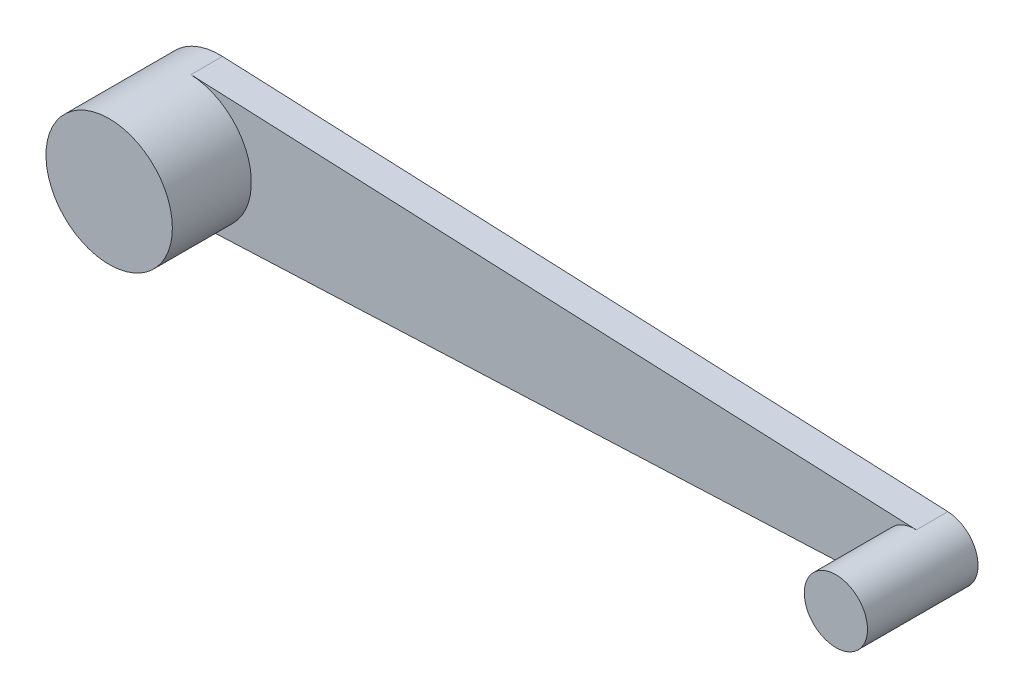
SolidWorks part; units mm, degrees
ref_plane "Front Plane" through (0, 0, 0) normal (0, 0, 1) x (1, 0, 0)
ref_plane "Top Plane" through (0, 0, 0) normal (0, 1, 0) x (1, 0, 0)
ref_plane "Right Plane" through (0, 0, 0) normal (1, 0, 0) x (0, 0, -1)
sketch "Sketch2" plane through (0, 0, 0) normal (0, 0, 1) x (1, 0, 0)
  line L0 (0, 0) -> (46, 0) construction
  line L2 (0.1739, 3.9962) -> (46.087, 1.9981)
  line L4 (0.1739, -3.9962) -> (46.087, -1.9981)
  circle A2 centre (0, 0) radius 4 construction
  circle A3 centre (46, 0) radius 2 construction
  arc A4 (0.1739, 3.9962) -> (0.1739, -3.9962) centre (0, 0) ccw
  arc A5 (46.087, 1.9981) -> (46.087, -1.9981) centre (46, 0) cw
  point P11 (0, 0)
extrude "Boss-Extrude1" add sketch "Sketch2" along normal blind 2
sketch "Sketch3" plane through (0, 0, 2) normal (0, 0, 1) x (1, 0, 0)
  circle A0 centre (0, 0) radius 4
  circle A1 centre (46, 0) radius 2
extrude "Boss-Extrude2" add sketch "Sketch3" along normal blind 5
